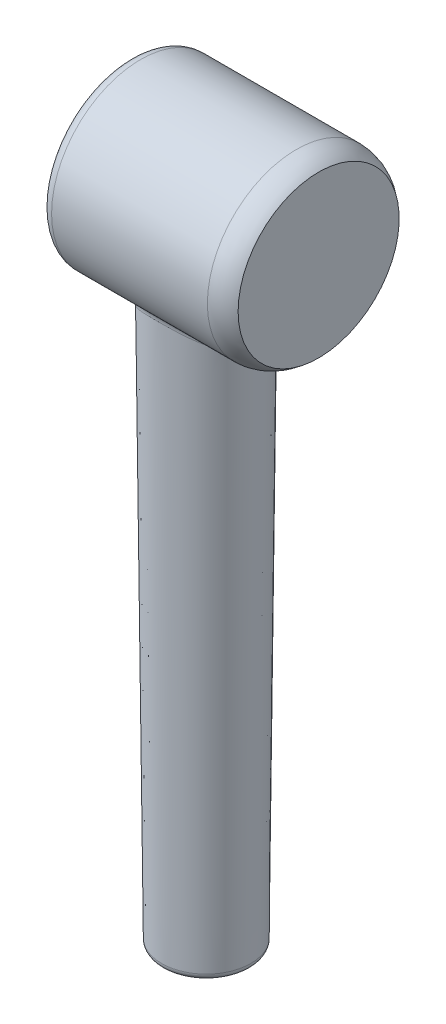
SolidWorks part; units mm, degrees
ref_plane "Front Plane" through (0, 0, 0) normal (0, 0, 1) x (1, 0, 0)
ref_plane "Top Plane" through (0, 0, 0) normal (0, 1, 0) x (1, 0, 0)
ref_plane "Right Plane" through (0, 0, 0) normal (1, 0, 0) x (0, 0, -1)
sketch "Sketch1" plane through (0, 0, 0) normal (0, 0, 1) x (1, 0, 0)
  line L0 (0, 128.3388) -> (0, 0) construction
  line L1 (0, 0) -> (119.2182, 0) construction
  line L6 (-55.114, 40) -> (84.2997, 40) construction
  line L7 (-34.5, 40) -> (-34.5, 0)
  line L8 (-34.5, 0) -> (50.5, 0)
  line L9 (50.5, 0) -> (50.5, 40)
  line L10 (50.5, 40) -> (-34.5, 40)
  line L11 (20, -250) -> (-20, -250)
  line L12 (-20, -250) -> (-22.9, 40)
  line L14 (0, -250) -> (0, 40)
  line L15 (20, -250) -> (22.9, 40) construction
  arc A0 (40.5, 0) -> (50.5, 3.8197) centre (40.5, 15) ccw
  point P4 (-22.5, 0)
  point P22 (22.5, 0)
  dimension "D7" = 10
  dimension "D8" = 15
  dimension "D1" = 40
  dimension "D2" = 12
  dimension "D3" = 22.5
  dimension "D4" = 20
  dimension "D5" = 250
  dimension "D6" = 85
revolve "Revolve1" add sketch "Sketch1" angle 360 about L6 region at (-28.5994, 19.887, 0) region at (-11.3503, 20.0587, 0) region at (25.1136, 20.1129, 0)
revolve "Revolve2" add sketch "Sketch1<3>" angle 360 about L0 region at (-11.3503, 20.0587, 0) region at (-10.6373, -122.549, 0)
sketch "Sketch1<3>" plane through (0, 0, 0) normal (0, 0, 1) x (1, 0, 0) same geometry as "Sketch1"
combine bodies "Combine1" operation type add bodies to combine 101 102
fillet "Fillet1" radius 5 2 edges at (14.8869, 3.7553, 16.921) (-34.5, 40, 40)
fillet "Fillet2" radius 3 1 edges at (0, -250, 20)
